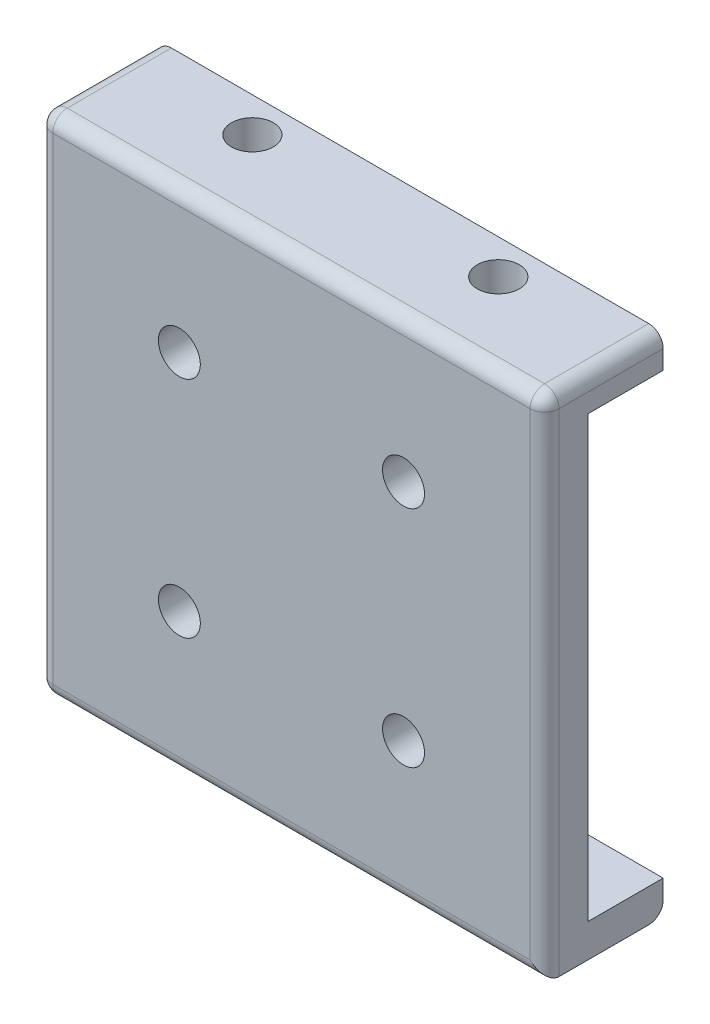
SolidWorks part; units mm, degrees
ref_plane "Plan de face" through (0, 0, 0) normal (0, 0, 1) x (1, 0, 0)
ref_plane "Plan de dessus" through (0, 0, 0) normal (0, 1, 0) x (1, 0, 0)
ref_plane "Plan de droite" through (0, 0, 0) normal (1, 0, 0) x (0, 0, -1)
sketch "Esquisse1" plane through (0, 0, 0) normal (0, 0, 1) x (1, 0, 0)
  line L1 (-20.4011, 23.115) -> (14.5989, 23.115)
  line L2 (-20.4011, 23.115) -> (-20.4011, -11.885)
  line L3 (-20.4011, -11.885) -> (14.5989, -11.885)
  line L4 (14.5989, 23.115) -> (14.5989, -11.885)
  point P4 (0, 0)
  point P5 (-40.8021, 23.115)
  dimension "D1" = 35
  dimension "D2" = 35
extrude "Boss.-Extru.1" add sketch "Esquisse1" along normal blind 3
sketch "Esquisse2" plane through (0, 0, 0) normal (0, 0, -1) x (-1, 0, 0)
  line L0 (20.4011, 23.115) -> (20.4011, -11.885) construction
  line L1 (-14.5989, 23.115) -> (20.4011, 23.115)
  line L2 (-14.5989, 23.115) -> (-14.5989, 20.815)
  line L3 (-14.5989, 20.815) -> (20.4011, 20.815)
  line L4 (20.4011, 23.115) -> (20.4011, 20.815)
  line L6 (-14.5989, -11.885) -> (20.4011, -11.885)
  line L7 (-14.5989, -11.885) -> (-14.5989, -9.585)
  line L8 (-14.5989, -9.585) -> (20.4011, -9.585)
  line L9 (20.4011, -11.885) -> (20.4011, -9.585)
  dimension "D1" = 2.3
extrude "Boss.-Extru.2" add sketch "Esquisse2" along normal blind 5.2
sketch "Esquisse3" plane through (0, 23.115, 0) normal (0, 1, 0) x (1, 0, 0)
  line L0 (-22.1328, 0) -> (16.7257, 0) construction
  line L1 (-22.1328, 2.8) -> (16.7257, 2.8) construction
  line L2 (-2.9011, 5.2) -> (-2.9011, -5.6538) construction
  line L3 (-20.4011, 5.2) -> (14.5989, 5.2) construction
  circle A0 centre (-11.4011, 2.8) radius 1.25
  circle A1 centre (5.5989, 2.8) radius 1.25
  point P13 (0, 0)
  dimension "D2" = 2.5
  dimension "D1" = 2.8
  dimension "D3" = 17
extrude "Enlèv. mat.-Extru.1" cut sketch "Esquisse3" against normal blind 45
sketch "Esquisse4" plane through (0, 0, 3) normal (0, 0, 1) x (1, 0, 0)
  line L0 (-2.9011, 23.115) -> (-2.9011, -11.885) construction
  line L1 (-10.6511, 13.365) -> (4.8489, 13.365) construction
  line L2 (-10.6511, 13.365) -> (-10.6511, -2.135) construction
  line L3 (-10.6511, -2.135) -> (4.8489, -2.135) construction
  line L4 (4.8489, 13.365) -> (4.8489, -2.135) construction
  line L5 (14.5989, 23.115) -> (-20.4011, 23.115) construction
  line L6 (-20.4011, -11.885) -> (14.5989, -11.885) construction
  line L7 (-20.4011, 23.115) -> (-20.4011, -11.885) construction
  line L8 (-20.4011, 5.615) -> (14.5989, 5.615) construction
  line L9 (14.5989, -11.885) -> (14.5989, 23.115) construction
  circle A0 centre (-10.6511, 13.365) radius 1.2
  circle A1 centre (4.8489, 13.365) radius 1.2
  circle A2 centre (4.8489, -2.135) radius 1.2
  circle A3 centre (-10.6511, -2.135) radius 1.2
  dimension "D2" = 2.4
  dimension "D1" = 15.5
hole_wizard "Dégagement M2.51" positions "Esquisse8" profile "Esquisse9" hole size "M2.5" standard "Ansi Metric" end condition through all
sketch "Esquisse8" plane through (0, 23.115, 0) normal (0, 1, 0) x (1, 0, 0)
  point P0 (-11.4011, 2.8)
  point P3 (5.5989, 2.8)
sketch "Esquisse9" plane through (-11.4011, 23.115, -2.8) normal (1, 0, 0) x (0, 0, 1)
  line L0 (0, 0) -> (0, 35)
  line L1 (0, 35) -> (1.45, 35)
  line L2 (1.45, 35) -> (1.45, 0)
  line L5 (1.45, 0) -> (0, 0)
  line L11 (0, -6.35) -> (0, 107.95) construction
  dimension "Diamètre du perçage jusqu'au prochain" = 2.9
  dimension "Profondeur du perçage jusqu'au prochain" = 35
hole_wizard "Dégagement M2.52" positions "Esquisse10" profile "Esquisse11" hole size "M2.5" standard "Ansi Metric" end condition through all
sketch "Esquisse10" plane through (0, -11.885, 0) normal (0, -1, 0) x (-1, 0, 0)
  point P0 (11.4011, 2.8)
  point P3 (-5.5989, 2.8)
sketch "Esquisse11" plane through (-11.4011, -11.885, -2.8) normal (1, 0, 0) x (0, 0, -1)
  line L0 (0, 0) -> (0, 35)
  line L1 (0, 35) -> (1.45, 35)
  line L2 (1.45, 35) -> (1.45, 0)
  line L5 (1.45, 0) -> (0, 0)
  line L11 (0, -6.35) -> (0, 107.95) construction
  dimension "Diamètre du perçage jusqu'au prochain" = 2.9
  dimension "Profondeur du perçage jusqu'au prochain" = 35
hole_wizard "Dégagement M2.53" positions "Esquisse12" profile "Esquisse13" hole size "M2.5" standard "Ansi Metric" end condition through all
sketch "Esquisse12" plane through (0, 0, 0) normal (0, 0, -1) x (-1, 0, 0)
  point P0 (-4.8489, 13.365)
  point P3 (10.6511, 13.365)
  point P6 (10.6511, -2.135)
  point P9 (-4.8489, -2.135)
sketch "Esquisse13" plane through (4.8489, 13.365, 0) normal (1, 0, 0) x (0, 1, 0)
  line L0 (0, 0) -> (0, 3)
  line L1 (0, 3) -> (1.45, 3)
  line L2 (1.45, 3) -> (1.45, 0)
  line L5 (1.45, 0) -> (0, 0)
  line L11 (0, -6.35) -> (0, 107.95) construction
  dimension "Diamètre du perçage jusqu'au prochain" = 2.9
  dimension "Profondeur du perçage jusqu'au prochain" = 3
fillet "Congé1" radius 1 8 edges at (-20.4011, -11.885, -1.1) (-20.4011, 23.115, -1.1) (-2.9011, -11.885, -5.2) (14.5989, 23.115, -1.1) (-2.9011, 23.115, 3) (14.5989, 5.615, 3) (-20.4011, 5.615, 3) (-2.9011, -11.885, 3)
